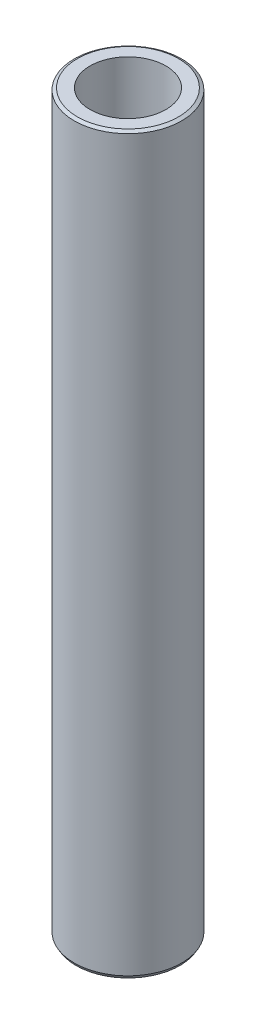
SolidWorks part; units mm, degrees
ref_plane "Front Plane" through (0, 0, 0) normal (0, 0, 1) x (1, 0, 0)
ref_plane "Top Plane" through (0, 0, 0) normal (0, 1, 0) x (1, 0, 0)
ref_plane "Right Plane" through (0, 0, 0) normal (1, 0, 0) x (0, 0, -1)
sketch "Sketch1" plane through (0, 0, 0) normal (0, 1, 0) x (1, 0, 0)
  circle A0 centre (0, 0) radius 27.5
  dimension "SHAFT_OD" = 55
extrude "Boss-Extrude1" add sketch "Sketch1" along normal blind 375.9537
sketch "Sketch2" plane through (0, 0, 0) normal (0, 1, 0) x (1, 0, 0)
  circle A0 centre (0, 0) radius 19.3995
  dimension "BORE_D" = 38.799
extrude "Cut-Extrude1" cut sketch "Sketch2" along normal through all
chamfer "Chamfer1" distance 0.9389 angle 60 2 edges at (0, 375.9537, 27.5) (0, 0, 27.5) first distance on face at (0, 375.9537, 27.5) first distance on face at (0, 0, 19.3995)
